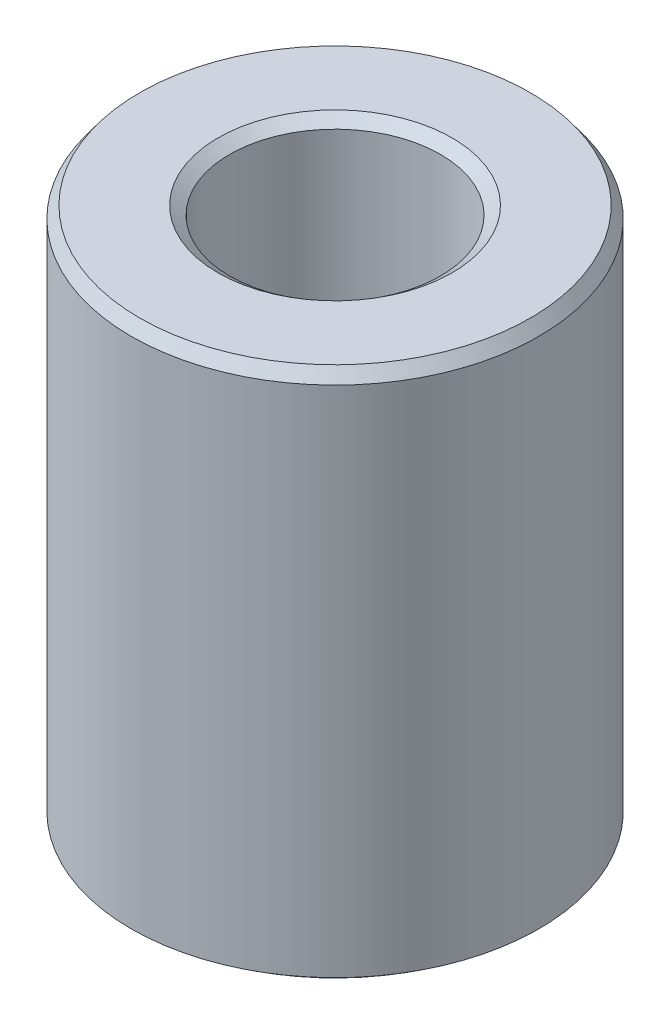
SolidWorks part; units mm, degrees
ref_plane "Front Plane" through (0, 0, 0) normal (0, 0, 1) x (1, 0, 0)
ref_plane "Top Plane" through (0, 0, 0) normal (0, 1, 0) x (1, 0, 0)
ref_plane "Right Plane" through (0, 0, 0) normal (1, 0, 0) x (0, 0, -1)
sketch "Sketch1" plane through (0, 0, 0) normal (0, 1, 0) x (1, 0, 0)
  circle A0 centre (0, 0) radius 25
  dimension "SLEEVE_OD" = 50
extrude "Boss-Extrude1" add sketch "Sketch1" along normal blind 65.4192
sketch "Sketch2" plane through (0, 0, 0) normal (0, 1, 0) x (1, 0, 0)
  circle A0 centre (0, 0) radius 12.9292
  dimension "BORE_D" = 25.8584
extrude "Cut-Extrude1" cut sketch "Sketch2" along normal through all
chamfer "Chamfer1" distance 1.423 angle 36.284 4 edges at (0, 65.4192, 12.9292) (0, 0, 12.9292) (0, 0, 25) (0, 65.4192, 25) first distance on face at (0, 65.4192, 12.9292) first distance on face at (0, 0, 12.9292) first distance on face at (0, 65.4192, 25)
